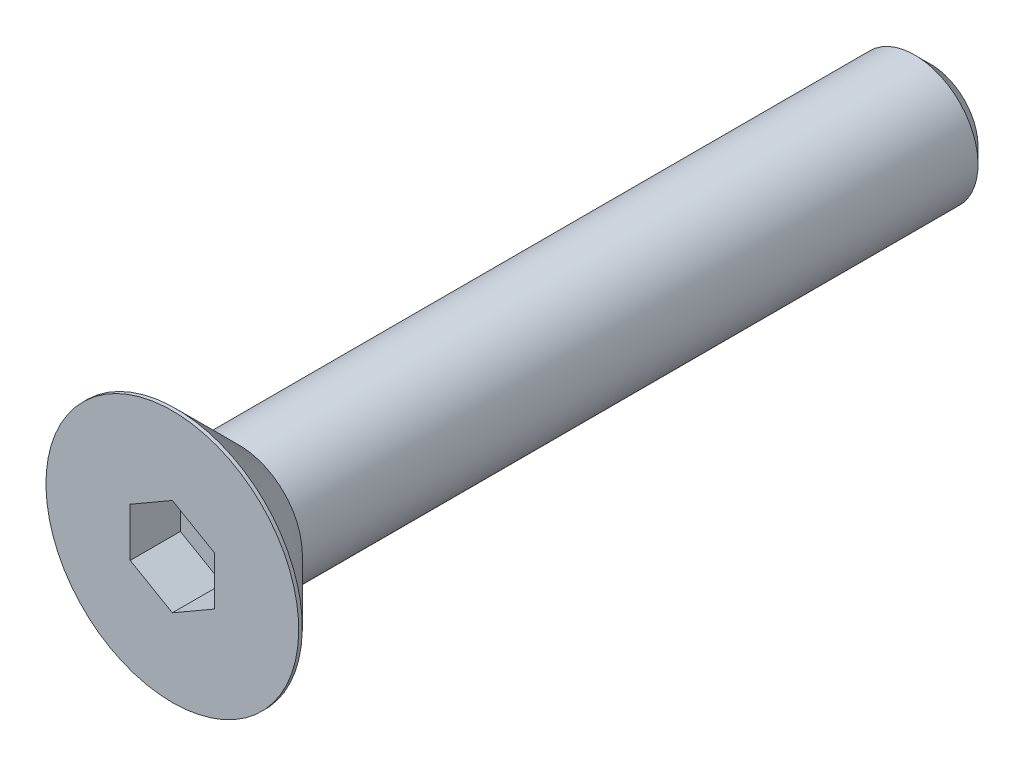
SolidWorks part; units mm, degrees
material "Chrome Stainless Steel"
ref_plane "Front" through (0, 0, 0) normal (0, 0, 1) x (1, 0, 0)
ref_plane "Top" through (0, 0, 0) normal (0, 1, 0) x (1, 0, 0)
ref_plane "Right" through (0, 0, 0) normal (1, 0, 0) x (0, 0, -1)
sketch "Sketch11" plane through (0, 0, 0) normal (1, 0, 0) x (0, 0, -1)
  line L0 (-9, 3) -> (9, 3) construction
  line L5 (-9, 3) -> (-9, -3) construction
  line L6 (9, 1.5) -> (9, -1.5) construction
  line L7 (-8.99, 1) -> (-8.99, -1) construction
  line L8 (8.9688, 1.5541) -> (9.4688, 1.5541) construction
  line L9 (9.4688, 1.5541) -> (9.2188, 1.1211) construction
  line L10 (9.2188, 1.1211) -> (8.9688, 1.5541) construction
  line L11 (9.1875, 1.1752) -> (9.25, 1.1752) construction
  line L12 (9.2188, 1.1752) -> (9.2188, 1.1211) construction
  line L13 (8.9844, 1.5271) -> (9.4531, 1.5271) construction
  line L14 (9.2188, 1.5541) -> (9.2188, 1.5) construction
  line L15 (9, 1.5) -> (9.4375, 1.5) construction
  line L17 (-8.915, 3) -> (-5.915, 0) construction
  line L18 (-5.915, 0) -> (-8.915, -3) construction
  point P3 (-7.3, 3)
  point P8 (0, 3)
  point P21 (9.2188, 1.5271)
  point P26 (-9, 0)
  point P28 (-8.99, 0)
  point P29 (9, 0)
  dimension "Length" = 18
  dimension "Head Diameter" = 6
  dimension "Thread Major Diameter" = 3
  dimension "Head Height" = 1.7
  dimension "Drive Size" = 2
  dimension "Thread Pitch" = 0.5
  dimension "D1" = 0.0625
  dimension "D2" = 0.01
  dimension "D3" = 0.085
  dimension "Countersink Angle" = 90
sketch "Sketch1" plane through (0, 0, 0) normal (1, 0, 0) x (0, 0, -1)
  line L2 (-7.3, 1.5) -> (9, 1.5)
  line L3 (9, 1.5) -> (9, 0)
  line L4 (-7.81, 1.5) -> (-7.81, 0)
  line L5 (-7.3, 1.5) -> (-7.81, 1.5)
  line L6 (-9, 3) -> (-9, -3) construction
  line L7 (9, 1.5) -> (9, -1.5) construction
  line L8 (-7.81, 0) -> (9, 0)
  dimension "D1" = 1.19
revolve "Revolve1" add sketch "Sketch1" angle 360 mid plane about L8
chamfer "Chamfer1" distance 0.375 angle 45 1 edges at (0, -1.5, -9)
sketch "Sketch7" plane through (0, 0, 0) normal (1, 0, 0) x (0, 0, -1)
  line L2 (-9, 3) -> (-8.915, 3)
  line L5 (-7.3, 1.385) -> (-7.3, 0)
  line L6 (-9, 3) -> (-9, 0)
  line L8 (-9, 3) -> (-9, -3) construction
  line L9 (-9, 0) -> (-7.3, 0)
  line L12 (-8.915, 3) -> (-7.3, 1.385)
  line L13 (-8.915, 3) -> (-5.915, 0) construction
revolve "Revolve2" add sketch "Sketch7" angle 360 mid plane about L9 region at (0, 1.1696, 8.2571)
ref_plane "Plane1" through (0, 0, 7.3) normal (0, 0, 1) x (1, 0, 0)
sketch "Sketch5" plane through (0, 0, 9) normal (0, 0, 1) x (1, 0, 0)
  line L1 (1, -0.5774) -> (1, 0.5774)
  line L2 (1, 0.5774) -> (0, 1.1547)
  line L3 (0, 1.1547) -> (-1, 0.5774)
  line L4 (-1, 0.5774) -> (-1, -0.5774)
  line L5 (-1, -0.5774) -> (0, -1.1547)
  line L6 (0, -1.1547) -> (1, -0.5774)
  circle A0 centre (0, 0) radius 1 construction
extrude "Cut-Extrude2" cut sketch "Sketch5" against normal blind 1.19
sketch "Sketch6" plane through (0, 0, 9) normal (0, 0, -1) x (-1, 0, 0)
  circle A0 centre (0, 0) radius 1.1547
extrude "Cut-Extrude3" [suppressed] cut sketch "Sketch6" along normal blind 1.19 draft 45
sketch "Sketch12" [suppressed] plane through (0, 0, -9) normal (0, 0, -1) x (-1, 0, 0)
  circle A0 centre (0, 0) radius 1.5 construction
  circle A1 centre (0, 0) radius 1.5
curve "Helix/Spiral1" [suppressed] pitch 0.5 height 18 turns 36
sketch "Sketch13" [suppressed] plane through (0, 0, 0) normal (1, 0, 0) x (0, 0, -1)
  line L0 (8.9844, 1.5271) -> (9.4531, 1.5271)
  line L1 (9.4531, 1.5271) -> (9.25, 1.1752)
  line L2 (9.25, 1.1752) -> (9.1875, 1.1752)
  line L3 (9.1875, 1.1752) -> (8.9844, 1.5271)
sweep "Cut-Sweep1" [suppressed] cut profiles "Sketch13" path "Helix/Spiral1"
combine bodies "Combine1" [suppressed] operation type add bodies to combine 113 127
equation "\"D1@Chamfer1\"=\"Thread Pitch@Sketch11\" * .75"
equation "\"D1@Cut-Extrude2\"= \"Head Height@Sketch11\" * .7"
equation "\"D1@Cut-Extrude3\" = \"D1@Cut-Extrude2\""
equation "\"D1@Sketch11\"=\"Thread Pitch@Sketch11\"/8"
equation "\"D3@Sketch11\"=\"Head Height@Sketch11\"*.05"
equation "\"D4@Helix/Spiral1\"=\"Thread Pitch@Sketch11\""
equation "\"D1@Sketch1\"=\"Head Height@Sketch11\"*.7"
equation "\"D3@Helix/Spiral1\"=\"Length@Sketch11\""
